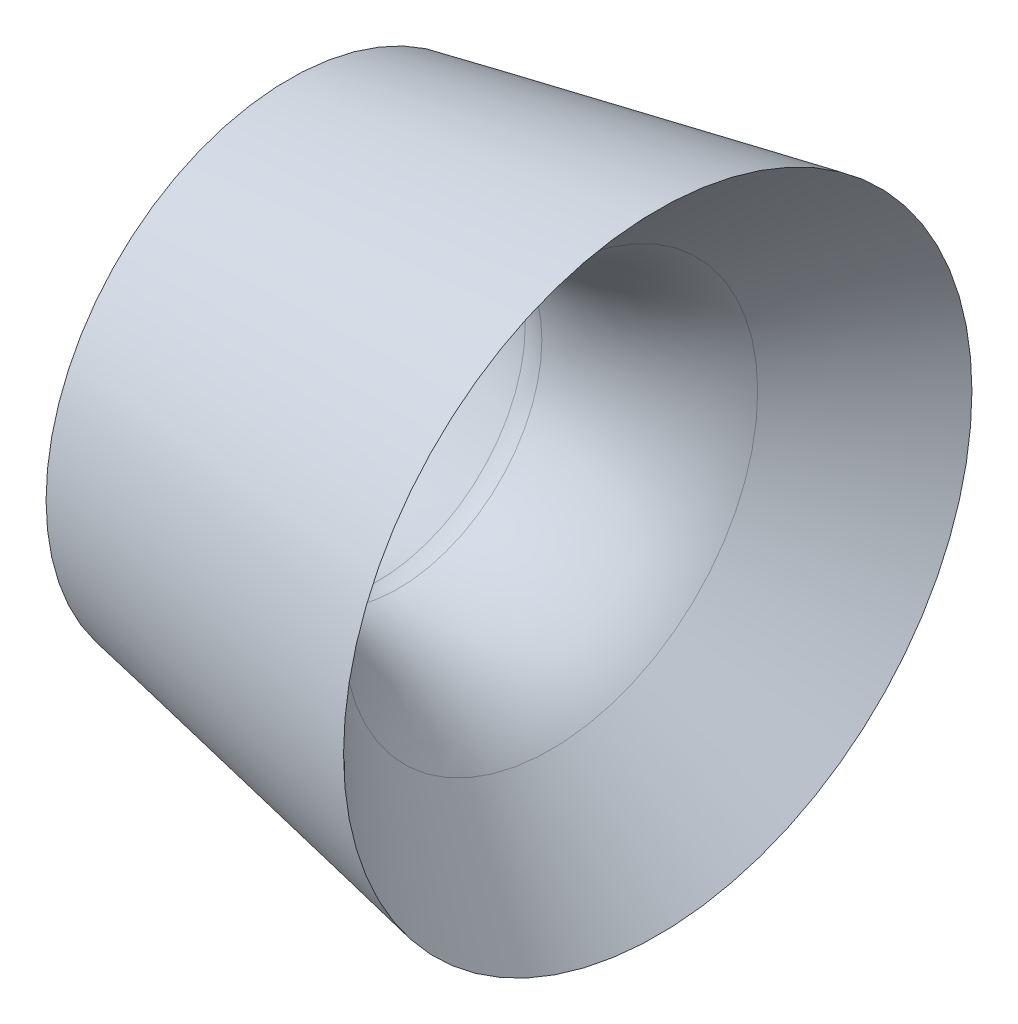
SolidWorks part; units mm, degrees
material "C (Graphite)"
ref_plane "Front Plane" through (0, 0, 0) normal (0, 0, 1) x (1, 0, 0)
ref_plane "Top Plane" through (0, 0, 0) normal (0, 1, 0) x (1, 0, 0)
ref_plane "Right Plane" through (0, 0, 0) normal (1, 0, 0) x (0, 0, -1)
sketch "Sketch1" plane through (0, 0, 0) normal (0, 0, 1) x (1, 0, 0)
  line L1 (0, 24.472) -> (-8.3426, 16.1295)
  line L3 (0, 0) -> (-30, 0) construction
  line L5 (-30, 18.6909) -> (-30, 14.6909) construction
  line L6 (-30, 18.6909) -> (-28.7014, 18.9412) construction
  line L8 (0, 24.472) -> (-30, 24.472) construction
  line L10 (0, 24.472) -> (0, 0) construction
  line L11 (-28.7014, 18.9412) -> (-28.7014, 14.2061)
  line L12 (-28.7014, 18.9412) -> (0, 24.472)
  arc A1 (-8.3426, 16.1295) -> (-20.2285, 11.2061) centre (-20.2285, 28.0154) cw
  arc A2 (-20.2285, 11.2061) -> (-21.8411, 11.5215) centre (-20.2285, 15.4869) cw
  arc A4 (-21.8411, 11.5215) -> (-28.7014, 14.2061) centre (-126.69, -246.3001) ccw
  arc A5 (-28.7014, 14.2061) -> (-30, 14.6909) centre (-126.69, -246.3001) ccw construction
  point P12 (-30, 14.6909)
  point P13 (-27.1828, 19.2338)
  dimension "D11" = 4.2807
  dimension "D12" = 16.8092
  dimension "D4" = 278.3258
  dimension "D6" = 4
  dimension "D20" = 30
  dimension "D3" = 10.907
  dimension "D5" = 24.472
  dimension "D7" = 11.2061
  dimension "D8" = 3
  dimension "D9" = 45
  dimension "D15" = 22.13
revolve "Revolve1" add sketch "Sketch1" angle 360 about L3 region at (-16.1948, 17.4006, 0)
equation "\"theta_t\"= 36.9009 - ( 426.271 / ( \"Aet\" + 7.00037 ) ) + ( 10026.8 / ( \"Aet\" + 7.00037 ) ^ 2 ) - ( 175410 / ( \"Aet\" + 7.00037 ) ^ 3 ) + ( ( 1.6742 * ( 10 ^ 6 ) ) / ( \"Aet\" + 7.00037 ) ^ 4 ) - ( ( 6.7643 * ( 10 ^ 6 ) ) / ( \"Aet\" + 7.00037 ) ^ 5 )"
equation "\"rt\"= ( 0.022412299 / 2 ) * 1000"
equation "\"re\"= sqr ( \"rt\" ^ 2 * \"Aet\" )"
equation "\"Aet\"= 4.317"
equation "\"L\"= 0.8 * ( ( \"re\" / tan ( 15 ) ) - ( \"rt\" / tan ( 15 ) ) )"
equation "\"lc\"= ( \"l*\" / \"cr\" )"
equation "\"b\"= tan ( \"theta_t\" )"
equation "\"a\"= ( \"re\" - \"b\" * \"L\" - \"c\" ) / \"L\" ^ 2"
equation "\"D11@Sketch1\"=0.382*\"rt\""
equation "\"D12@Sketch1\"=1.5*\"rt\""
equation "\"c\"= \"rt\" * ( 1.382 - 0.382 * cos ( \"theta_t\" ) )"
equation "\"D15@Sketch1\"=\"theta_t\""
equation "\"cr\"= 5.978857531"
equation "\"rc\"= sqr ( \"cr\" * ( \"rt\" ^ 2 ) )"
equation "\"l*\"= 1000"
equation "\"th\"= 10"
equation "\"theta_cr\"= 45deg"
equation "\"D9@Sketch1\"=\"theta_cr\""
